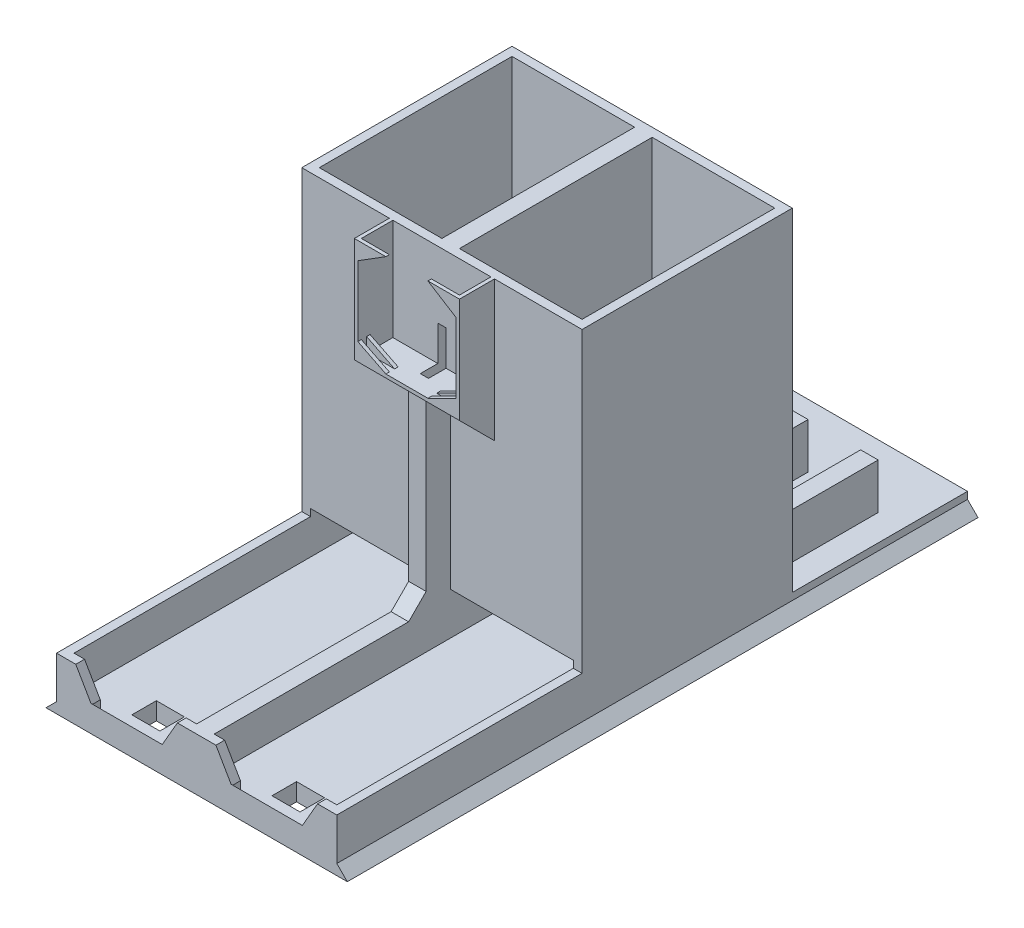
SolidWorks part; units mm, degrees
ref_plane "Front Plane" through (0, 0, 0) normal (0, 0, 1) x (1, 0, 0)
ref_plane "Top Plane" through (0, 0, 0) normal (0, 1, 0) x (1, 0, 0)
ref_plane "Right Plane" through (0, 0, 0) normal (1, 0, 0) x (0, 0, -1)
sketch "Sketch1" plane through (0, 0, 0) normal (0, 1, 0) x (1, 0, 0)
  line L1 (0, 0) -> (80, 0)
  line L2 (0, 0) -> (0, 60)
  line L3 (0, 60) -> (80, 60)
  line L4 (80, 0) -> (80, 60)
sketch "Sketch2" plane through (0, 0, 0) normal (0, 1, 0) x (1, 0, 0)
  line L1 (2.5, 57.5) -> (37.5, 57.5)
  line L2 (2.5, 57.5) -> (2.5, 2.5)
  line L3 (2.5, 2.5) -> (37.5, 2.5)
  line L4 (37.5, 57.5) -> (37.5, 2.5)
  line L5 (42.5, 57.5) -> (77.5, 57.5)
  line L6 (42.5, 57.5) -> (42.5, 2.5)
  line L7 (42.5, 2.5) -> (77.5, 2.5)
  line L8 (77.5, 57.5) -> (77.5, 2.5)
  dimension "D1" = 35
extrude "Boss-Extrude1" add sketch "Sketch1" along normal blind 100
extrude "Cut-Extrude1" cut sketch "Sketch2" along normal blind 95 from offset 5
sketch "Sketch3" plane through (0, 0, 0) normal (0, 0, 1) x (1, 0, 0)
  line L0 (80, 100) -> (80, 0) construction
  line L1 (0, 0) -> (80, 0)
  line L2 (0, 0) -> (0, 5)
  line L3 (0, 5) -> (80, 5)
  line L4 (80, 0) -> (80, 5)
extrude "Boss-Extrude2" add sketch "Sketch3" along normal blind 70
sketch "Sketch4" plane through (0, 5, 0) normal (0, 1, 0) x (1, 0, 0)
  line L0 (80, 0) -> (77.5, 0)
  line L5 (0, 0) -> (0, -70)
  line L18 (0, -70) -> (80, -70)
  line L19 (80, -70) -> (80, 0)
  line L20 (80, 0) -> (0, 0) construction
  line L21 (77.5, 0) -> (77.5, -67.5)
  line L22 (77.5, -67.5) -> (42.5, -67.5)
  line L23 (42.5, -67.5) -> (42.5, 0)
  line L24 (0, 0) -> (80, 0) construction
  line L25 (42.5, 0) -> (37.5, 0)
  line L26 (37.5, 0) -> (37.5, -67.5)
  line L27 (37.5, -67.5) -> (2.5, -67.5)
  line L28 (2.5, -67.5) -> (2.5, 0)
  line L29 (2.5, 0) -> (0, 0)
extrude "Boss-Extrude3" add sketch "Sketch4" along normal blind 10
sketch "Sketch5" plane through (0, 15, 0) normal (0, 1, 0) x (1, 0, 0)
  line L0 (37.5, -67.5) -> (2.5, -67.5) construction
  line L1 (10, -67.5) -> (30, -67.5)
  line L2 (10, -67.5) -> (10, -70)
  line L3 (10, -70) -> (30, -70)
  line L4 (30, -67.5) -> (30, -70)
  line L5 (0, -70) -> (80, -70) construction
  line L6 (77.5, -67.5) -> (42.5, -67.5) construction
  line L7 (70, -67.5) -> (50, -67.5)
  line L8 (70, -67.5) -> (70, -70)
  line L9 (70, -70) -> (50, -70)
  line L10 (50, -67.5) -> (50, -70)
  line L12 (37.5, 0) -> (37.5, -67.5) construction
  line L13 (42.5, -67.5) -> (42.5, 0) construction
  line L14 (77.5, 0) -> (77.5, -67.5) construction
  line L15 (2.5, -67.5) -> (2.5, 0) construction
  dimension "D1" = 7.5
  dimension "D2" = 7.5
  dimension "D3" = 7.5
  dimension "D4" = 7.5
extrude "Cut-Extrude2" cut sketch "Sketch5" against normal blind 7.5
sketch "Sketch6" plane through (0, 0, 0) normal (0, 0, 1) x (1, 0, 0)
  line L1 (2.5, 17) -> (37.5, 17)
  line L2 (2.5, 17) -> (2.5, 5)
  line L3 (2.5, 5) -> (37.5, 5)
  line L4 (37.5, 17) -> (37.5, 5)
  line L5 (42.5, 5) -> (77.5, 5)
  line L6 (42.5, 5) -> (42.5, 17)
  line L7 (42.5, 17) -> (77.5, 17)
  line L8 (77.5, 5) -> (77.5, 17)
extrude "Cut-Extrude4" cut sketch "Sketch6" against normal blind 57.5
sketch "Sketch7" plane through (0, 0, -60) normal (0, 0, -1) x (-1, 0, 0)
  circle A0 centre (-20, 11.5) radius 4
  circle A1 centre (-60, 11.5) radius 4
extrude "Cut-Extrude6" cut sketch "Sketch7" against normal up to next
sketch "Sketch9" plane through (0, 0, 0) normal (0, 1, 0) x (1, 0, 0)
  line L1 (0, 60) -> (80, 60)
  line L2 (0, 60) -> (0, 110)
  line L3 (0, 110) -> (80, 110)
  line L4 (80, 60) -> (80, 110)
extrude "Boss-Extrude4" add sketch "Sketch9" along normal blind 5
sketch "Sketch13" plane through (0, 5, 0) normal (0, 1, 0) x (1, 0, 0)
  line L1 (16, -64.5) -> (24, -64.5)
  line L2 (16, -64.5) -> (16, -57.5)
  line L3 (16, -57.5) -> (24, -57.5)
  line L4 (24, -64.5) -> (24, -57.5)
  line L5 (30, -67.5) -> (10, -67.5) construction
  line L10 (2.5, 57.5) -> (2.5, -67.5) construction
  line L11 (37.5, -67.5) -> (37.5, 57.5) construction
  line L12 (40, -70) -> (40, -52.9537) construction
  line L13 (30, -70) -> (50, -70) construction
  line L15 (56, -64.5) -> (56, -57.5)
  line L16 (64, -57.5) -> (56, -57.5)
  line L17 (64, -64.5) -> (64, -57.5)
  line L18 (64, -64.5) -> (56, -64.5)
  point P12 (16, -61)
  dimension "D1" = 13.5
  dimension "D2" = 13.5
  dimension "D3" = 7
  dimension "D4" = 3
extrude "Cut-Extrude8 (Button Holes)" cut sketch "Sketch13" against normal through all
sketch "Sketch14" plane through (0, 0, 0) normal (0, 0, 1) x (1, 0, 0)
  line L0 (0, 100) -> (80, 100) construction
  line L1 (25, 100) -> (26, 100)
  line L2 (25, 100) -> (25, 70)
  line L3 (25, 70) -> (26, 70)
  line L4 (26, 100) -> (26, 71)
  line L6 (54, 100) -> (55, 100)
  line L7 (54, 100) -> (54, 71)
  line L8 (54, 70) -> (55, 70)
  line L9 (55, 100) -> (55, 70)
  line L10 (26, 70) -> (54, 70)
  line L12 (26, 71) -> (54, 71)
  dimension "D1" = 30
  dimension "D2" = 1
  dimension "D3" = 1
extrude "Boss-Extrude5 (OLED Mount)" add sketch "Sketch14" along normal blind 10
sketch "Sketch15" plane through (0, 0, 10) normal (0, 0, 1) x (1, 0, 0)
  line L6 (40, 70) -> (40, 81.9127) construction
  line L7 (25, 70) -> (55, 70) construction
  line L8 (26, 71) -> (26, 100) construction
  line L14 (26, 71) -> (34, 71)
  line L15 (54, 71) -> (26, 71) construction
  line L16 (34, 71) -> (26, 75)
  line L17 (26, 75) -> (26, 71)
  line L18 (54, 75) -> (54, 71)
  line L19 (46, 71) -> (54, 75)
  line L20 (54, 71) -> (46, 71)
  dimension "D1" = 8
  dimension "D2" = 4
  dimension "D3" = 14
sketch "Sketch17" plane through (0, 0, 10) normal (0, 0, 1) x (1, 0, 0)
  line L0 (40, 100) -> (40, 89.7245) construction
  line L9 (26, 100) -> (54, 100) construction
  line L10 (54, 95) -> (54, 100)
  line L11 (46, 100) -> (54, 95)
  line L12 (26, 100) -> (34, 100)
  line L13 (34, 100) -> (26, 95)
  line L14 (26, 71) -> (26, 100) construction
  line L15 (26, 95) -> (26, 100)
  line L16 (54, 100) -> (46, 100)
  dimension "D1" = 8
  dimension "D2" = 5
extrude "Boss-Extrude6 (OLED Mount)" add sketch "Sketch15" against normal blind 1
extrude "Boss-Extrude7 (OLED Mount)" add sketch "Sketch15<2>" against normal blind 1 from offset 2.5 offset against normal yes
sketch "Sketch15<2>" plane through (0, 0, 10) normal (0, 0, 1) x (1, 0, 0) same geometry as "Sketch15"
extrude "Boss-Extrude8 (OLED Mount)" add sketch "Sketch17" against normal blind 1
sketch "Sketch32" plane through (25, 0, 0) normal (-1, 0, 0) x (0, 0, 1)
  line L0 (0, 70) -> (10, 70)
  line L1 (10, 70) -> (0, 60)
  line L3 (0, 60) -> (0, 70)
  line L4 (0, 15) -> (0, 17) construction
extrude "Boss-Extrude13 OLED Mount Support)" add sketch "Sketch32" against normal blind 30
sketch "Sketch18" plane through (0, 71, 0) normal (0, 1, 0) x (1, 0, 0)
  line L0 (26, 0) -> (54, 0) construction
  line L5 (42.5, 57.5) -> (42.5, -67.5) construction
  line L8 (38.82, 3) -> (41.18, 3)
  line L9 (38.82, 3) -> (38.82, -5)
  line L10 (38.82, -5) -> (41.18, -5)
  line L11 (41.18, 3) -> (41.18, -5)
  line L12 (37.5, -67.5) -> (37.5, 57.5) construction
  dimension "D1" = 1.32
  dimension "D2" = 1.32
  dimension "D3" = 3
  dimension "D4" = 5
extrude "Cut-Extrude9 (OLED Cable)" cut sketch "Sketch18" against normal through all and the other way blind 10
sketch "Sketch31" plane through (0, 15, 0) normal (0, 1, 0) x (1, 0, 0)
  line L0 (37.5, 0) -> (38.82, 0)
  line L1 (38.82, 0) -> (38.82, -5)
  line L2 (38.82, -5) -> (41.18, -5)
  line L3 (41.18, -5) -> (41.18, 0)
  line L4 (41.18, 0) -> (42.5, 0)
  line L5 (42.5, 0) -> (42.5, -7)
  line L6 (42.5, -7) -> (37.5, -7)
  line L7 (37.5, 0) -> (37.5, -67.5) construction
  line L8 (37.5, -7) -> (37.5, 0)
  dimension "D1" = 2
extrude "Boss-Extrude12 (OLED Cable Guide)" add sketch "Sketch31" along normal up to next
sketch "Sketch20" plane through (0, 5, 0) normal (0, 1, 0) x (1, 0, 0)
  line L0 (0, 60) -> (80, 60) construction
  line L1 (65, 60) -> (55, 60)
  line L2 (65, 60) -> (65, 70)
  line L3 (65, 70) -> (55, 70)
  line L4 (55, 60) -> (55, 70)
  line L5 (80, 60) -> (80, 110) construction
  line L7 (40, 110) -> (40, 60) construction
  line L8 (80, 110) -> (0, 110) construction
  line L9 (15, 70) -> (25, 70)
  line L10 (25, 60) -> (25, 70)
  line L11 (15, 60) -> (25, 60)
  line L12 (15, 60) -> (15, 70)
  point P8 (60, 60)
  dimension "D1" = 10
  dimension "D2" = 15
  dimension "D3" = 10
  dimension "D4" = 40
extrude "Cut-Extrude10 (Solenoid Wire Hole)" cut sketch "Sketch20" against normal through all
sketch "Sketch21" plane through (0, 5, 0) normal (0, 1, 0) x (1, 0, 0)
  line L0 (65, 60) -> (80, 60) construction
  line L1 (67.5, 60) -> (72.5, 60)
  line L2 (67.5, 60) -> (67.5, 92)
  line L3 (67.5, 92) -> (72.5, 92)
  line L4 (72.5, 60) -> (72.5, 92)
  line L7 (80, 110) -> (0, 110) construction
  line L9 (40, 60) -> (40, 110) construction
  line L10 (25, 60) -> (55, 60) construction
  line L11 (0, 110) -> (0, 60) construction
  line L12 (60, 110) -> (60, 60) construction
  line L13 (80, 60) -> (80, 110) construction
  line L15 (47.5, 60) -> (47.5, 92)
  line L16 (52.5, 92) -> (47.5, 92)
  line L17 (52.5, 60) -> (52.5, 92)
  line L18 (52.5, 60) -> (47.5, 60)
  line L19 (27.5, 60) -> (32.5, 60)
  line L20 (27.5, 60) -> (27.5, 92)
  line L21 (32.5, 60) -> (32.5, 92)
  line L22 (27.5, 92) -> (32.5, 92)
  line L23 (7.5, 60) -> (7.5, 92)
  line L24 (12.5, 92) -> (7.5, 92)
  line L25 (12.5, 60) -> (12.5, 92)
  line L26 (12.5, 60) -> (7.5, 60)
  dimension "D1" = 5
  dimension "D2" = 40
  dimension "D3" = 20
  dimension "D4" = 7.5
  dimension "D5" = 32
extrude "Boss-Extrude9 (Solenoid Side Support)" add sketch "Sketch21" along normal blind 13
chamfer "Chamfer3 (Thumb)" distance 2.5 angle 45 2 edges at (20, 7.5, 67.5) (60, 7.5, 67.5)
chamfer "Chamfer5 (Thumb)" distance 4.5 angle 60 4 edges at (70, 15, 68.75) (50, 15, 68.75) (30, 15, 68.75) (10, 15, 68.75) first distance on face at (75.8333, 15, 45.8333) first distance on face at (40, 15, 53) first distance on face at (4.1667, 15, 45.8333)
sketch "Sketch37" plane through (0, 0, 70) normal (0, 0, 1) x (1, 0, 0)
  line L0 (80, 0) -> (83, 0)
  line L1 (83, 0) -> (80, 3)
  line L2 (80, 0) -> (80, 15) construction
  line L3 (80, 3) -> (80, 0)
  line L4 (0, 0) -> (-3, 0)
  line L5 (-3, 0) -> (0, 3)
  line L6 (0, 15) -> (0, 0) construction
  line L7 (0, 3) -> (0, 0)
  dimension "D1" = 3
  dimension "D2" = 3
  dimension "D3" = 3
  dimension "D4" = 3
extrude "Boss-Extrude5 (Guide)" add sketch "Sketch37" against normal through all
sketch "Sketch49" plane through (0, 15, 0) normal (0, 1, 0) x (1, 0, 0)
  line L0 (42.5, -67.5) -> (42.5, -7) construction
  line L1 (37.5, -7) -> (42.5, -7)
  line L2 (37.5, -7) -> (37.5, -12)
  line L3 (37.5, -12) -> (42.5, -12)
  line L4 (42.5, -7) -> (42.5, -12)
  dimension "D1" = 5
extrude "Boss-Extrude14" add sketch "Sketch49" along normal blind 5
chamfer "Chamfer8" distance 5 angle 45 1 edges at (40, 20, 12)
